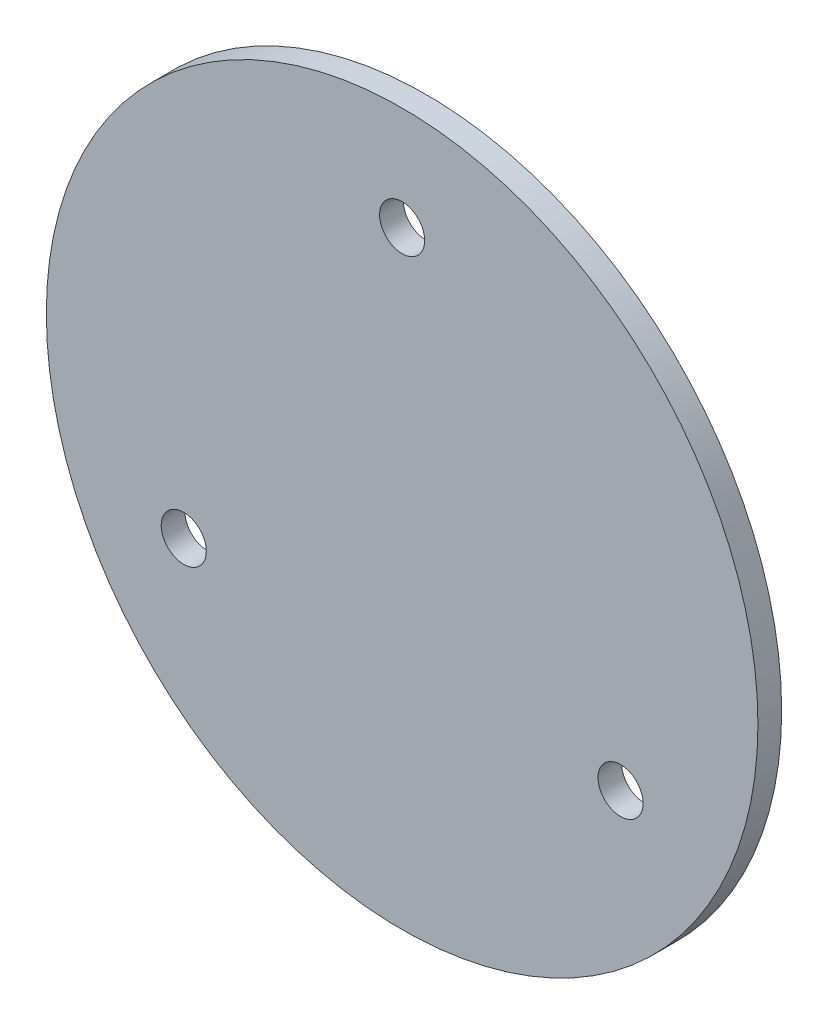
SolidWorks part; units mm, degrees
ref_plane "正面" through (0, 0, 0) normal (0, 0, 1) x (1, 0, 0)
ref_plane "平面" through (0, 0, 0) normal (0, 1, 0) x (1, 0, 0)
ref_plane "右側面" through (0, 0, 0) normal (1, 0, 0) x (0, 0, -1)
sketch "ｽｹｯﾁ1" plane through (0, 0, 0) normal (0, 0, 1) x (1, 0, 0)
  circle A0 centre (0, 0) radius 30
  dimension "D1" = 60
extrude "ﾎﾞｽ - 押し出し1" add sketch "ｽｹｯﾁ1" along normal blind 2
sketch "ｽｹｯﾁ2" plane through (0, 0, 0) normal (0, 0, 1) x (1, 0, 0)
  circle A0 centre (0, 0) radius 21.263 construction
  circle A1 centre (0, 21.263) radius 1.9
  circle A2 centre (18.4143, -10.6315) radius 1.9
  circle A3 centre (-18.4143, -10.6315) radius 1.9
  point P6 (0, 0)
  point P7 (-21.8052, -12.5892)
  point P11 (0, 0)
  dimension "D1" = 42.526
  dimension "D2" = 3.8
  dimension "D3" = 3
extrude "ｶｯﾄ - 押し出し1" cut sketch "ｽｹｯﾁ2" against normal through all both and the other way through all
equation "\"D1@ｽｹｯﾁ2\"=21.263mm*2"
